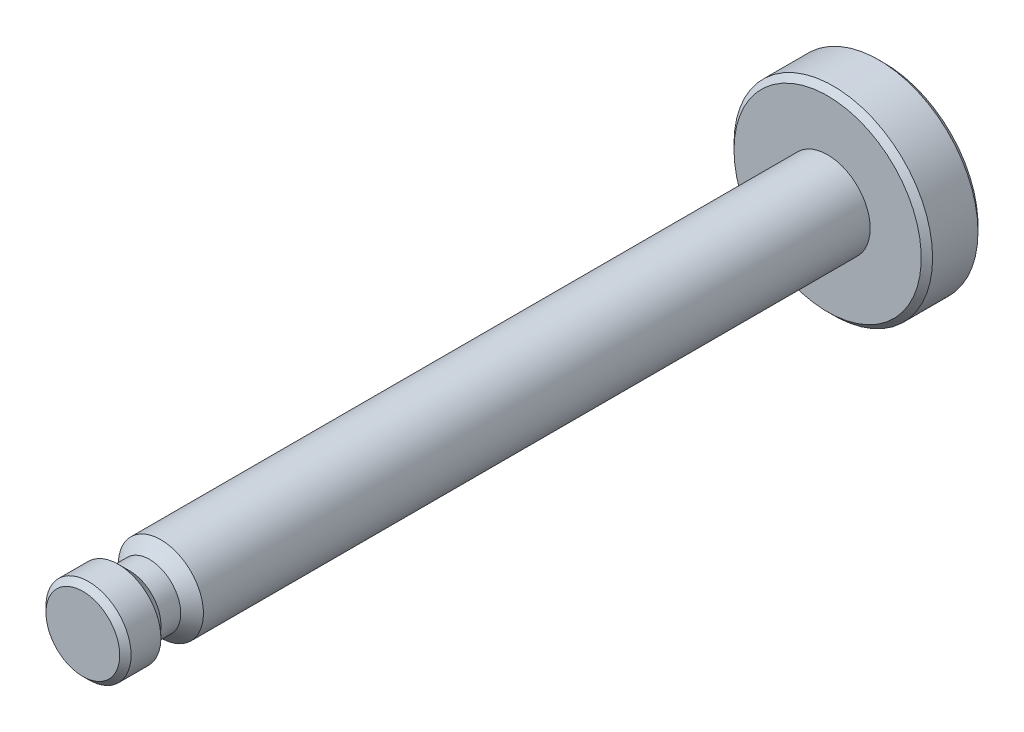
SolidWorks part; units mm, degrees
ref_plane "Front" through (0, 0, 0) normal (0, 0, 1) x (1, 0, 0)
ref_plane "Top" through (0, 0, 0) normal (0, 1, 0) x (1, 0, 0)
ref_plane "Right" through (0, 0, 0) normal (1, 0, 0) x (0, 0, -1)
sketch "Sketch2" plane through (0, 0, 0) normal (0, 0, 1) x (1, 0, 0)
  circle A0 centre (0, 0) radius 1.5
  dimension "D1" = 3
extrude "Shaft" add sketch "Sketch2" along normal blind 26.25
sketch "Sketch3" plane through (0, 0, 0) normal (0, 0, -1) x (-1, 0, 0)
  circle A3 centre (0, 0) radius 3.5
  dimension "D1" = 7
extrude "Head" add sketch "Sketch3" along normal blind 2
sketch "Sketch4" plane through (0, 0, 0) normal (1, 0, 0) x (0, 0, -1)
  line L0 (0, 0) -> (-24.25, 0) construction
  line L1 (-24.25, 0) -> (-24.25, 4.3666) construction
  line L2 (-25, 1.5) -> (-23.5, 1.5)
  line L3 (0, 1.5) -> (-26.25, 1.5) construction
  line L6 (-23.5, 1.5) -> (-23.9, 1.1)
  line L7 (-23.9, 1.1) -> (-24.6, 1.1)
  line L8 (-24.6, 1.1) -> (-25, 1.5)
  dimension "D1" = 24.25
  dimension "D2" = 1.5
  dimension "D3" = 45
  dimension "D4" = 0.4
revolve "e-Clip Notch" cut sketch "Sketch4" angle 360 about L0
chamfer "Deburs" distance 0.2 angle 45 3 edges at (1.5, 0, 26.25) (-3.5, 0, 0) (-3.5, 0, -2)
equation "\"D1@Shaft\"=\"Hardware Length@Box Assy.Assembly\"+6.25mm"
equation "\"D1@Sketch4\"=\"Hardware Length@Box Assy.Assembly\" + 4.25mm"
equation "\"D1@Sketch2\"=\"Hardware Clearance Hole Diameter@Box Assy.Assembly\"-.15"
